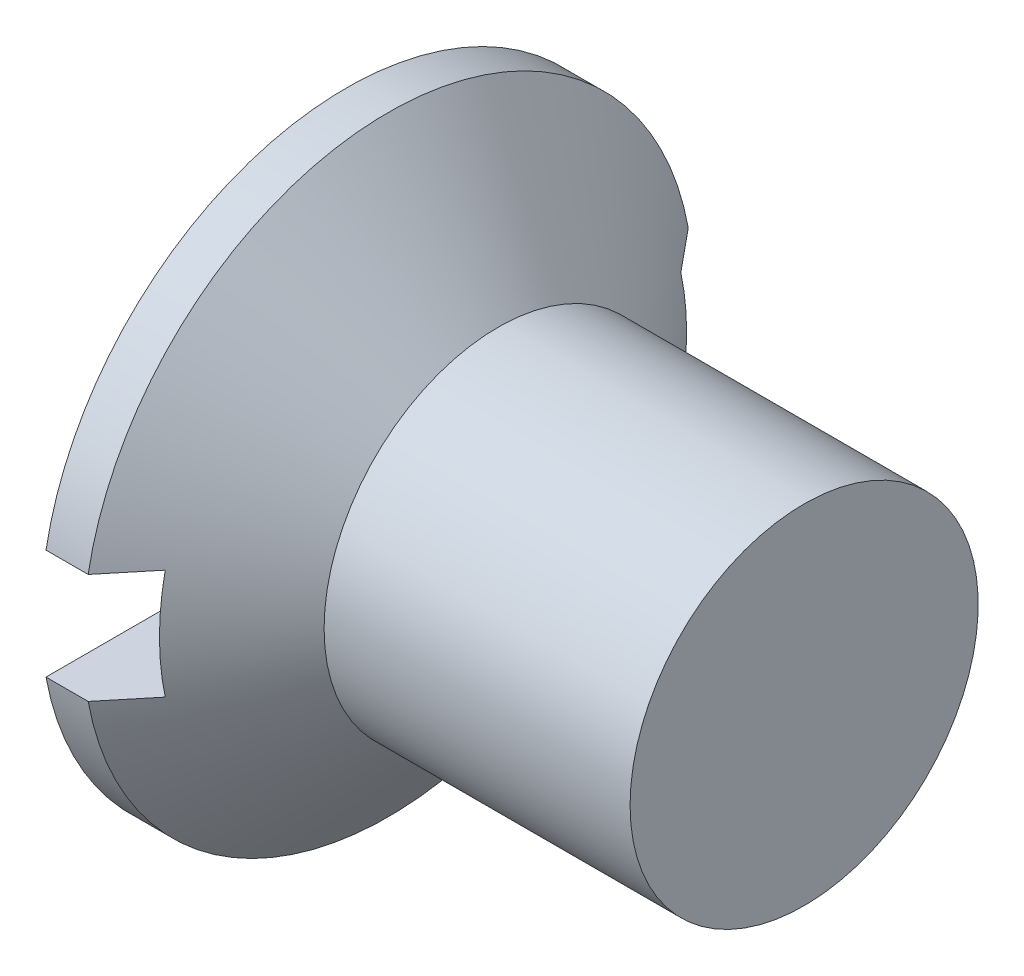
SolidWorks part; units mm, degrees
revolve "Base-Revolve" add sketch "BodySke" angle 360 about L5
sketch "BodySke" plane through (0, 0, 0) normal (0, 0, 1) x (1, 0, 0)
  line L0 (0, 0) -> (0, 4.2291)
  line L1 (0, 4.2291) -> (0.5843, 4.2291)
  line L2 (2.1082, 2.413) -> (6.35, 2.413)
  line L3 (6.35, 2.413) -> (6.35, 0)
  line L4 (6.35, 0) -> (0, 0)
  line L5 (-6.35, 0) -> (82.55, 0) construction
  line L6 (2.1082, -2.413) -> (6.35, -2.413) construction
  line L7 (0.5843, -4.2291) -> (2.1082, -2.413) construction
  line L8 (0.5843, 4.2291) -> (2.1082, 2.413)
  line L9 (0, -4.2291) -> (0.5843, -4.2291) construction
  line L10 (3.1674, 4.0005) -> (3.1674, -5.5245) construction
  line L11 (0, 6.35) -> (0, -3.175) construction
  dimension "D6" = 0.5843
  dimension "Diameter" = 4.826
cosmetic thread "ThreadCosmetic" [suppressed] parameters "Thread_length"=3.1826, "Thread_minor"=3.5662
extrude "Slot" cut sketch "Sketch2" against normal blind 1.0668
sketch "Sketch2" plane through (0, 0, 0) normal (-1, 0, 0) x (0, 0, 1)
  line L0 (-4.2291, -0.762) -> (4.2291, -0.762)
  line L1 (-4.2291, -0.762) -> (-4.2291, 0.762)
  line L2 (4.2291, 0.762) -> (-4.2291, 0.762)
  line L3 (4.2291, 0.762) -> (4.2291, -0.762)
  dimension "D1" = 0.762
  dimension "D2" = 8.4582
  dimension "D3" = 4.2291
material "Stainless Steel (ferritic)"
ref_plane "Plane1" through (0, 0, 0) normal (0, 0, 1) x (1, 0, 0)
ref_plane "Plane2" through (0, 0, 0) normal (0, 1, 0) x (1, 0, 0)
ref_plane "Plane3" through (0, 0, 0) normal (1, 0, 0) x (0, 0, -1)
sketch "Sketch3" plane through (0, 0, 0) normal (-1, 0, 0) x (0, 0, 1)
  line L0 (-0.5334, 2.8575) -> (0.5334, 2.8575)
  line L1 (0.5334, 2.8575) -> (0.5334, -2.8575)
  line L2 (0.5334, -2.8575) -> (-0.5334, -2.8575)
  line L3 (-0.5334, -2.8575) -> (-0.5334, 2.8575)
  dimension "Cross_dia" = 5.715
  dimension "Cross_width" = 1.0668
  dimension "D1" = 2.8575
  dimension "D2" = 0.5334
ref_plane "Plane4" through (3.7338, 0, 0) normal (-1, 0, 0) x (0, 0, 1)
sketch "Sketch4" plane through (3.7338, 0, 0) normal (-1, 0, 0) x (0, 0, 1)
  line L0 (-0.2667, 0.2667) -> (0.2667, 0.2667)
  line L3 (0.2667, 0.2667) -> (0.2667, -0.2667)
  line L4 (0.2667, -0.2667) -> (-0.2667, -0.2667)
  line L5 (-0.2667, -0.2667) -> (-0.2667, 0.2667)
  dimension "D2" = 0.5334
  dimension "D1" = 0.5334
  dimension "D3" = 0.2667
  dimension "D4" = 0.2667
loft "Cross" cut profiles "Sketch3", "Sketch4"
pattern_circular "CirPattern1" count 2 every 90 about axis through (-6.35, 0, 0) along (1, 0, 0) of "Cross"
sketch "ThdSchSke" plane through (0, 0, 0) normal (0, 0, 1) x (1, 0, 0)
  line L0 (3.1674, -1.7831) -> (2.7263, -2.413)
  line L1 (3.1674, -1.7831) -> (3.6085, -2.413)
  line L2 (3.6085, -2.413) -> (3.6085, -3.0162)
  line L3 (-3.175, 0) -> (5.1513, 0) construction
  line L5 (3.6085, -3.0162) -> (2.7263, -3.0162)
  line L6 (2.7263, -3.0162) -> (2.7263, -2.413)
  line L7 (0, 4.2291) -> (0, 0.762) construction
  dimension "Thread_minor" = 3.5662
  dimension "Diameter" = 4.826
  dimension "Start" = 3.1674
revolve "ThreadSchematic" [suppressed] cut sketch "ThdSchSke" angle 360 about L3
pattern_linear "ThdSchPat" [suppressed]
equation "\"D1@Sketch3\" = \"Cross_dia@Sketch3\" / 2"
equation "\"D2@Sketch3\" = \"Cross_width@Sketch3\" / 2"
equation "\"D1@Sketch4\" = \"Cross_width@Sketch3\" *.5"
equation "\"D2@Sketch4\" = \"D1@Sketch4\""
equation "\"D4@Sketch4\" = \"D2@Sketch4\" / 2"
equation "\"D3@Sketch4\" = \"D1@Sketch4\" / 2"
equation "\"D1@Sketch2\" = \"Slot_width@Sketch2\" / 2"
equation "\"D2@Sketch2\" = \"Head_dia@BodySke\""
equation "\"D3@Sketch2\" = \"D2@Sketch2\" / 2"
equation "\"Thread_length@ThreadCosmetic\" = ((sgn( (\"Length@BodySke\" - \"Advance@BodySke\" - \"Head_ht@BodySke\" ) - \"Thread_nom@BodySke\" )-1)*( (\"Length@BodySke\" - \"Advance@BodySke\" - \"Head_ht@BodySke\" ) - \"Thread_nom@BodySke\" ))/-2+ \"Thread_nom@BodySke\""
equation "\"Thread_minor@ThdSchSke\" = \"Thread_minor@ThreadCosmetic\""
equation "\"Diameter@ThdSchSke\" = \"Diameter@BodySke\""
equation "\"Overcut@ThdSchSke\" = \"Diameter@BodySke\" * 1.25"
equation "\"Start@ThdSchSke\" = 0.000001 + \"Length@BodySke\" - \"Thread_length@ThreadCosmetic\"  '---Countersunk---"
equation "\"Num_threads@ThdSchPat\" = int( \"Thread_length@ThreadCosmetic\" / \"Advance@BodySke\" + 0.999 )  + 1"
equation "\"Advance@ThdSchPat\" = \"Thread_length@ThreadCosmetic\" /  (\"Num_threads@ThdSchPat\" - 1) 'relax it"
